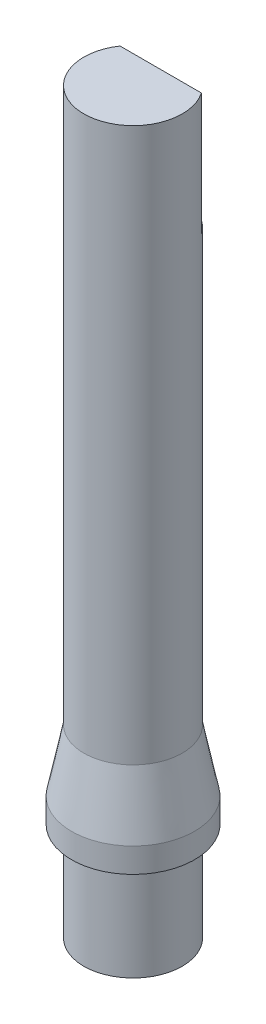
SolidWorks part; units mm, degrees
ref_plane "Front Plane" through (0, 0, 0) normal (0, 0, 1) x (1, 0, 0)
ref_plane "Top Plane" through (0, 0, 0) normal (0, 1, 0) x (1, 0, 0)
ref_plane "Right Plane" through (0, 0, 0) normal (1, 0, 0) x (0, 0, -1)
sketch "Sketch1" plane through (0, 0, 0) normal (0, 1, 0) x (1, 0, 0)
  circle A0 centre (0, 0) radius 4
  dimension "D1" = 8
extrude "Boss-Extrude1" add sketch "Sketch1" along normal blind 60
ref_plane "Plane1" through (0, 8, 0) normal (0, -1, 0) x (-1, 0, 0)
sketch "Sketch2" plane through (0, 8, 0) normal (0, -1, 0) x (-1, 0, 0)
  circle A0 centre (0, 0) radius 5
  circle A1 centre (0, 0) radius 4 construction
  dimension "D1" = 10
extrude "Boss-Extrude2" add sketch "Sketch2" against normal blind 2
chamfer "Chamfer1" distance 5 distance2 1 1 edges at (0, 10, -4) first distance on face at (0, 60, 4)
sketch "Sketch3" plane through (0, 60, 0) normal (0, 1, 0) x (1, 0, 0)
  line L0 (-3.3072, 2.25) -> (3.3072, 2.25)
  circle A0 centre (0, 0) radius 4 construction
  arc A1 (3.3072, 2.25) -> (-3.3072, 2.25) centre (0, 0) ccw
  point P4 (0, 4)
  point P8 (0, 0)
  dimension "D1" = 1.75
extrude "Cut-Extrude1" cut sketch "Sketch3" against normal blind 10
ref_axis "Axis1" through (0, 60, 0) along (0, -1, 0)
